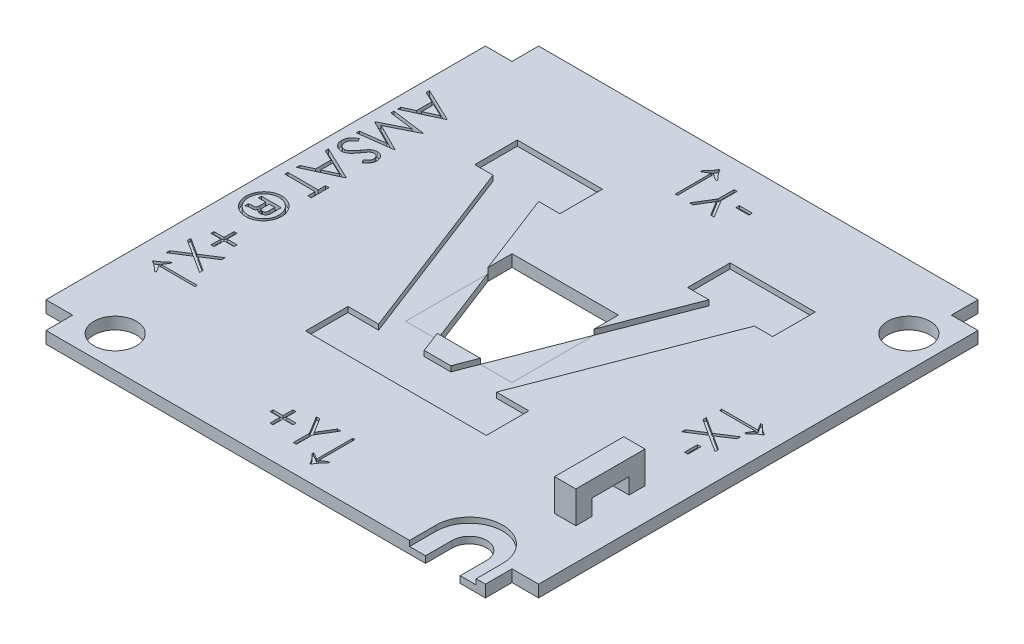
SolidWorks part; units mm, degrees
ref_plane "Front" through (0, 0, 0) normal (0, 0, 1) x (1, 0, 0)
ref_plane "Top" through (0, 0, 0) normal (0, 1, 0) x (1, 0, 0)
ref_plane "Right" through (0, 0, 0) normal (1, 0, 0) x (0, 0, -1)
sketch "Sketch2" plane through (0, 0, 0) normal (0, 1, 0) x (1, 0, 0)
  line L1 (-46.3, 41.3) -> (46.3, 41.3)
  line L2 (-46.3, 41.3) -> (-46.3, -41.3)
  line L3 (-46.3, -41.3) -> (46.3, -41.3)
  line L4 (46.3, 41.3) -> (46.3, -41.3)
  line L5 (-46.3, 41.3) -> (46.3, -41.3) construction
  line L6 (-46.3, -41.3) -> (46.3, 41.3) construction
  line L7 (-41.3, 46.3) -> (41.3, 46.3)
  line L8 (-41.3, 46.3) -> (-41.3, -46.3)
  line L9 (-41.3, -46.3) -> (41.3, -46.3)
  line L10 (41.3, 46.3) -> (41.3, -46.3)
  line L11 (-41.3, 46.3) -> (41.3, -46.3) construction
  line L12 (-41.3, -46.3) -> (41.3, 46.3) construction
  point P0 (0, 0)
  point P6 (0, 0)
  dimension "D1" = 82.6
  dimension "D2" = 92.6
  dimension "D3" = 92.6
  dimension "D4" = 82.6
extrude "Boss-Extrude1" add sketch "Sketch2" along normal blind 2.25 contours L8 L1 L2 L3 | L10 L1 L8 L3 | L10 L3 L8 L9 | L1 L10 L3 L4 | L10 L7 L8 L1 region at (-43.8, 0, 0) region at (0, 0, -43.8) region at (0, 0, 0) region at (43.8, 0, 0) region at (0, 0, 43.8)
sketch "Sketch3" plane through (0, 2.25, 0) normal (0, 1, 0) x (1, 0, 0)
  line L0 (-41.3, 46.3) -> (41.3, 46.3) construction
  line L1 (-46.3, 41.3) -> (-46.3, -41.3) construction
  line L2 (46.3, 41.3) -> (46.3, -41.3) construction
  line L3 (-41.3, -46.3) -> (41.3, -46.3) construction
  circle A0 centre (-34.3, -40.3) radius 4
  circle A1 centre (40.3, 34.3) radius 4
  dimension "D1" = 8
  dimension "D2" = 8
  dimension "D3" = 6
  dimension "D4" = 12
  dimension "D5" = 12
  dimension "D6" = 6
extrude "Cut-Extrude1" cut sketch "Sketch3" against normal blind 10
sketch "Sketch4" plane through (0, 2.25, 0) normal (0, 1, 0) x (1, 0, 0)
  line L1 (-38.2288, 21.7712) -> (-18.2288, 21.7712)
  line L2 (-38.2288, 21.7712) -> (-38.2288, -8.2288)
  line L3 (-38.2288, -8.2288) -> (-18.2288, -8.2288)
  line L4 (-18.2288, 21.7712) -> (-18.2288, -8.2288)
  line L5 (-8.2288, 38.2288) -> (21.7712, 38.2288)
  line L6 (-8.2288, 38.2288) -> (-8.2288, 18.2288)
  line L7 (-8.2288, 18.2288) -> (21.7712, 18.2288)
  line L8 (21.7712, 38.2288) -> (21.7712, 18.2288)
  line L9 (38.2288, -21.7712) -> (18.2288, -21.7712)
  line L10 (38.2288, -21.7712) -> (38.2288, 8.2288)
  line L11 (38.2288, 8.2288) -> (18.2288, 8.2288)
  line L12 (18.2288, -21.7712) -> (18.2288, 8.2288)
  line L13 (8.2288, -18.2288) -> (-21.7712, -18.2288)
  line L14 (8.2288, -18.2288) -> (8.2288, -38.2288)
  line L15 (8.2288, -38.2288) -> (-21.7712, -38.2288)
  line L16 (-21.7712, -18.2288) -> (-21.7712, -38.2288)
  circle A0 centre (0, 0) radius 20 construction
  dimension "D11" = 40
  dimension "D1" = 20
  dimension "D2" = 30
  dimension "D3" = 10
  dimension "D4" = 30
  dimension "D5" = 20
  dimension "D6" = 30
  dimension "D7" = 20
  dimension "D8" = 30
  dimension "D9" = 20
  dimension "D10" = 10
  dimension "D12" = 10
  dimension "D13" = 10
extrude "Cut-Extrude2" [suppressed] cut sketch "Sketch4" against normal blind 10
sketch "Sketch5" plane through (0, 2.25, 0) normal (0, 1, 0) x (1, 0, 0)
  line L0 (30.05, -41.3) -> (30.05, -46.3)
  line L1 (-41.3, -46.3) -> (41.3, -46.3) construction
  line L2 (30.05, -46.3) -> (36.55, -46.3)
  line L3 (36.55, -46.3) -> (36.55, -41.3)
  line L4 (46.3, 41.3) -> (46.3, -41.3) construction
  arc A0 (30.05, -41.3) -> (36.55, -41.3) centre (33.3, -41.3) cw
  dimension "D1" = 5
  dimension "D2" = 3.25
  dimension "D3" = 13
extrude "Cut-Extrude3" cut sketch "Sketch5" against normal blind 10
sketch "Sketch6" plane through (0, 2.25, 0) normal (0, 1, 0) x (1, 0, 0)
  line L0 (27.05, -46.3) -> (27.05, -41.3)
  line L1 (-41.3, -46.3) -> (30.05, -46.3) construction
  line L2 (39.55, -46.3) -> (39.55, -41.3)
  line L4 (27.05, -41.3) -> (30.05, -41.3) construction
  line L5 (36.55, -46.3) -> (41.3, -46.3) construction
  line L8 (36.55, -46.3) -> (36.55, -41.3) construction
  line L9 (39.55, -41.3) -> (36.55, -41.3) construction
  line L10 (27.05, -46.3) -> (30.05, -46.3)
  line L11 (30.05, -46.3) -> (30.05, -41.3)
  line L12 (30.05, -41.3) -> (36.55, -41.3)
  line L13 (36.55, -41.3) -> (36.55, -46.3)
  line L14 (36.55, -46.3) -> (39.55, -46.3)
  arc A0 (27.05, -41.3) -> (39.55, -41.3) centre (33.3, -41.3) cw
  point P13 (39.55, -43.8)
  dimension "D3" = 6.25
  dimension "D1" = 3
  dimension "D2" = 3
extrude "Cut-Extrude4" cut sketch "Sketch6" against normal blind 1
sketch "Sketch7" plane through (0, 2.25, 0) normal (0, 1, 0) x (1, 0, 0)
  line L1 (-10, 10) -> (10, 10)
  line L2 (-10, 10) -> (-10, -10)
  line L3 (-10, -10) -> (10, -10)
  line L4 (10, 10) -> (10, -10)
  line L5 (-10, 10) -> (10, -10) construction
  line L6 (-10, -10) -> (10, 10) construction
  point P0 (0, 0)
  dimension "D1" = 20
  dimension "D2" = 20
extrude "Cut-Extrude5" cut sketch "Sketch7" against normal blind 10
sketch "Sketch9" [suppressed] plane through (0, 2.25, 0) normal (0, 1, 0) x (1, 0, 0)
  line L0 (-38.2288, -8.2288) -> (-18.2288, -8.2288) construction
  line L1 (-38.2288, 21.7712) -> (-31.2481, 21.7712)
  line L2 (-38.2288, 21.7712) -> (-38.2288, -8.2288)
  line L3 (-38.2288, -8.2288) -> (-31.2481, -8.2288)
  line L4 (-31.2481, 21.7712) -> (-31.2481, -8.2288)
extrude "Boss-Extrude2" [suppressed] add sketch "Sketch9" against normal blind 2.25
sketch "Sketch12" plane through (0, 2.25, 0) normal (0, 1, 0) x (1, 0, 0)
  line L1 (-44.3, 29.112) -> (-44.3, -7.0645) construction
  line L2 (-46.3, 41.3) -> (-46.3, -41.3) construction
  text T0 "AMSAT"
  dimension "D1" = 2
extrude "Cut-Extrude9" cut sketch "Sketch12" against normal blind 1
sketch "Sketch18" plane through (0, 2.25, 0) normal (0, 1, 0) x (1, 0, 0)
  line L0 (-24.5745, 21) -> (-11.0745, -14)
  line L1 (-28, 29) -> (-12, 29)
  line L2 (-28, 29) -> (-28, 21)
  line L3 (-28, 21) -> (-12, 21)
  line L4 (-12, 29) -> (-12, 21)
  line L5 (12, 29) -> (28, 29)
  line L6 (12, 29) -> (12, 21)
  line L7 (12, 21) -> (28, 21)
  line L8 (28, 29) -> (28, 21)
  line L9 (-16.8241, -14) -> (17.1759, -14)
  line L10 (-16.8241, -14) -> (-16.8241, -22)
  line L11 (-16.8241, -22) -> (17.1759, -22)
  line L12 (17.1759, -14) -> (17.1759, -22)
  line L13 (-11.0745, -14) -> (-2.5, -14)
  line L14 (-2.5, -14) -> (-16, 21)
  line L15 (2.5, -14) -> (16, 21)
  line L16 (24.5745, 21) -> (11.0745, -14)
  line L17 (0, 0) -> (0, -14) construction
  line L18 (-24.5745, 21) -> (-16, 21) construction
  line L19 (-10, -10) -> (10, -10) construction
  line L20 (16, 21) -> (24.5745, 21) construction
  point P25 (20, 21)
  dimension "D1" = 8
  dimension "D2" = 8
  dimension "D3" = 2.5
  dimension "D4" = 2.5
  dimension "D5" = 34
  dimension "D6" = 8
  dimension "D7" = 8
  dimension "D8" = 8
  dimension "D9" = 16
  dimension "D10" = 16
  dimension "D11" = 35
  dimension "D12" = 4
  dimension "D13" = 12
  dimension "D14" = 12
  dimension "D15" = 4
  dimension "D16" = 4
sketch "Sketch21" plane through (0, 2.25, 0) normal (0, 1, 0) x (1, 0, 0)
  line L0 (-44.3, 28.7864) -> (-44.3, -17.5036) construction
  line L1 (-44.3, -2.3211) -> (-37.9588, -2.3211) construction
  line L2 (-44.3, -2.3211) -> (-44.3, -24.4995) construction
  line L3 (-39.1712, -4.1935) -> (-39.1712, -5.7759)
  line L4 (-41.8971, -7.1243) -> (-42.3194, -7.1243)
  line L5 (-42.8168, -7.2909) -> (-42.916, -7.3685)
  line L6 (-42.916, -7.3685) -> (-42.916, -6.6358)
  line L7 (-42.4276, -6.5747) -> (-42.0205, -6.5544)
  line L8 (-41.5321, -5.7696) -> (-41.5321, -4.7634)
  line L9 (-41.5321, -4.7634) -> (-42.916, -4.7634)
  line L10 (-42.916, -4.7634) -> (-42.916, -4.1935)
  line L11 (-42.916, -4.1935) -> (-39.1712, -4.1935)
  line L12 (-39.8224, -4.7634) -> (-40.8808, -4.7634)
  line L13 (-40.8808, -4.7634) -> (-40.8808, -5.7288)
  line L14 (-39.8224, -5.767) -> (-39.8224, -4.7634)
  spline S0 degree 3 poles (-41.0372, -8.9967) (-41.185, -8.9949) (-41.4059, -8.984) (-41.695, -8.9354) (-41.9066, -8.8858) (-42.1141, -8.8224) (-42.3174, -8.7439) (-42.517, -8.6528) (-42.7113, -8.5469) (-42.8987, -8.4297) (-43.0761, -8.3001) (-43.2448, -8.1618) (-43.4023, -8.0112) (-43.5504, -7.8507) (-43.6877, -7.6793) (-43.8172, -7.499) (-43.9327, -7.3071) (-44.0386, -7.1097) (-44.1298, -6.9072) (-44.2087, -6.7017) (-44.27, -6.4915) (-44.3201, -6.2789) (-44.3686, -5.9894) (-44.3797, -5.7685) (-44.3814, -5.6207) knots 0 0 0 0 0.084082 0.125371 0.166472 0.207567 0.248614 0.290246 0.3322 0.374331 0.415745 0.457006 0.498264 0.539545 0.581027 0.623028 0.665647 0.708239 0.750309 0.791807 0.833294 0.874629 0.915918 1 1 1 1
  spline S1 degree 3 poles (-44.3814, -5.6207) (-44.3796, -5.473) (-44.3688, -5.2515) (-44.3197, -4.9619) (-44.2724, -4.7485) (-44.2073, -4.5397) (-44.132, -4.3329) (-44.0394, -4.1309) (-43.9357, -3.9326) (-43.8194, -3.7417) (-43.6918, -3.56) (-43.5527, -3.39) (-43.405, -3.2288) (-43.2468, -3.0786) (-43.0789, -2.9382) (-42.9, -2.8096) (-42.7123, -2.6922) (-42.5189, -2.5849) (-42.3193, -2.4938) (-42.1173, -2.4139) (-41.9108, -2.3508) (-41.7014, -2.3009) (-41.4165, -2.2526) (-41.199, -2.2413) (-41.0538, -2.2397) knots 0 0 0 0 0.084269 0.125889 0.167262 0.208679 0.250411 0.292575 0.335148 0.377862 0.419817 0.461544 0.502916 0.544266 0.585774 0.627475 0.6697 0.711864 0.753369 0.794595 0.83555 0.876272 0.917177 1 1 1 1
  spline S2 degree 3 poles (-41.0538, -2.2397) (-40.9072, -2.2412) (-40.6876, -2.2528) (-40.4002, -2.3007) (-40.1891, -2.3508) (-39.981, -2.4142) (-39.777, -2.4935) (-39.5756, -2.5852) (-39.38, -2.6921) (-39.1899, -2.8092) (-39.0095, -2.9382) (-38.8408, -3.0786) (-38.6806, -3.2276) (-38.5319, -3.388) (-38.3938, -3.5593) (-38.2673, -3.7414) (-38.1498, -3.9315) (-38.0469, -4.1294) (-37.9537, -4.3306) (-37.8781, -4.5369) (-37.8155, -4.7468) (-37.7653, -4.9599) (-37.7203, -5.2511) (-37.704, -5.4722) (-37.7058, -5.6207) knots 0 0 0 0 0.083231 0.124457 0.16526 0.206291 0.24781 0.289377 0.331805 0.374278 0.416018 0.457555 0.498758 0.540138 0.581556 0.62355 0.665898 0.708311 0.750097 0.791671 0.832863 0.874368 0.915793 1 1 1 1
  spline S3 degree 3 poles (-37.7058, -5.6207) (-37.7041, -5.7692) (-37.7201, -5.9904) (-37.7656, -6.281) (-37.8141, -6.4939) (-37.8766, -6.703) (-37.9531, -6.9082) (-38.0436, -7.1096) (-38.1476, -7.3057) (-38.2632, -7.4954) (-38.39, -7.6758) (-38.5281, -7.8455) (-38.6763, -8.0054) (-38.8353, -8.1553) (-39.0044, -8.2956) (-39.1852, -8.4244) (-39.3744, -8.5433) (-39.571, -8.6495) (-39.7707, -8.743) (-39.974, -8.8209) (-40.1807, -8.8842) (-40.3903, -8.9357) (-40.6754, -8.9835) (-40.8923, -8.9953) (-41.0372, -8.9967) knots 0 0 0 0 0.084514 0.12609 0.167457 0.208799 0.250299 0.292137 0.334491 0.376661 0.41861 0.459992 0.501181 0.542701 0.584388 0.62628 0.669037 0.711619 0.753439 0.794572 0.835522 0.876529 0.917429 1 1 1 1
  spline S4 degree 3 poles (-41.0436, -8.5082) (-40.9191, -8.5073) (-40.7328, -8.4969) (-40.4891, -8.4555) (-40.3097, -8.4134) (-40.1331, -8.359) (-39.9597, -8.2909) (-39.789, -8.2118) (-39.6215, -8.1223) (-39.4605, -8.0203) (-39.307, -7.9101) (-39.1618, -7.7914) (-39.0277, -7.662) (-38.8994, -7.5267) (-38.7831, -7.3804) (-38.6722, -7.2281) (-38.5746, -7.0654) (-38.4851, -6.898) (-38.4079, -6.7262) (-38.3408, -6.5515) (-38.2878, -6.3727) (-38.2454, -6.191) (-38.2067, -5.9431) (-38.1945, -5.7546) (-38.1942, -5.6284) knots 0 0 0 0 0.083087 0.124099 0.164782 0.205936 0.24722 0.288982 0.331375 0.373829 0.415981 0.457375 0.498787 0.540211 0.581645 0.623403 0.665799 0.70806 0.74996 0.791407 0.832749 0.874259 0.915784 1 1 1 1
  spline S5 degree 3 poles (-38.1942, -5.6284) (-38.1944, -5.5012) (-38.2068, -5.3115) (-38.2452, -5.0623) (-38.288, -4.8798) (-38.341, -4.6998) (-38.4078, -4.5229) (-38.4851, -4.3486) (-38.5745, -4.1786) (-38.6722, -4.0134) (-38.7831, -3.8586) (-38.8991, -3.7098) (-39.0273, -3.573) (-39.1623, -3.4439) (-39.3061, -3.3234) (-39.461, -3.2151) (-39.6214, -3.1127) (-39.7891, -3.0235) (-39.9597, -2.9435) (-40.1344, -2.878) (-40.3116, -2.8224) (-40.4925, -2.7811) (-40.7387, -2.7392) (-40.9267, -2.7291) (-41.0525, -2.7281) knots 0 0 0 0 0.084266 0.125816 0.167074 0.208434 0.250155 0.292315 0.334816 0.377436 0.419398 0.46102 0.502398 0.543559 0.58488 0.626613 0.668809 0.710945 0.752453 0.793648 0.834552 0.875536 0.916576 1 1 1 1
  spline S6 degree 3 poles (-41.0525, -2.7281) (-41.1774, -2.7291) (-41.3641, -2.7393) (-41.6082, -2.7809) (-41.7874, -2.8226) (-41.963, -2.878) (-42.1364, -2.9435) (-42.3058, -3.0235) (-42.4721, -3.1128) (-42.6312, -3.2146) (-42.7838, -3.3243) (-42.9273, -3.4435) (-43.0617, -3.573) (-43.1872, -3.7114) (-43.305, -3.8587) (-43.4144, -4.0147) (-43.5132, -4.18) (-43.6014, -4.3506) (-43.6797, -4.5245) (-43.7461, -4.7011) (-43.7994, -4.8814) (-43.8416, -5.064) (-43.8807, -5.3127) (-43.8926, -5.5017) (-43.8929, -5.6284) knots 0 0 0 0 0.083161 0.124071 0.164652 0.205433 0.246513 0.287914 0.329953 0.372063 0.413487 0.454957 0.496062 0.537606 0.579157 0.621501 0.664274 0.707178 0.749231 0.791103 0.832611 0.874292 0.915713 1 1 1 1
  spline S7 degree 3 poles (-43.8929, -5.6284) (-43.8929, -5.7543) (-43.8801, -5.9421) (-43.8424, -6.1896) (-43.7975, -6.3704) (-43.745, -6.5493) (-43.6783, -6.7246) (-43.6005, -6.8972) (-43.5107, -7.0654) (-43.4099, -7.2275) (-43.3028, -7.3836) (-43.1836, -7.5283) (-43.0571, -7.6647) (-42.9241, -7.794) (-42.7803, -7.9121) (-42.6295, -8.0235) (-42.4693, -8.1228) (-42.3041, -8.2137) (-42.1344, -8.2921) (-41.9611, -8.3589) (-41.7848, -8.4137) (-41.604, -8.4556) (-41.3577, -8.4967) (-41.1694, -8.5076) (-41.0436, -8.5082) knots 0 0 0 0 0.083922 0.125442 0.166735 0.208071 0.249777 0.291673 0.33431 0.376848 0.418899 0.460506 0.501732 0.542934 0.584104 0.625793 0.667851 0.709742 0.751498 0.792411 0.833559 0.874512 0.916077 1 1 1 1
  spline S8 degree 3 poles (-39.1712, -5.7759) (-39.1708, -5.862) (-39.1733, -5.9864) (-39.1852, -6.1455) (-39.1983, -6.2502) (-39.2129, -6.3455) (-39.2316, -6.431) (-39.2548, -6.5064) (-39.2878, -6.5944) (-39.3428, -6.6921) (-39.4239, -6.7982) (-39.5231, -6.8928) (-39.6383, -6.9754) (-39.7682, -7.0407) (-39.9595, -7.1088) (-40.115, -7.1221) (-40.2193, -7.1243) knots 0 0 0 0 0.131786 0.190365 0.24397 0.293257 0.337811 0.377839 0.413992 0.48137 0.548473 0.617773 0.690341 0.764636 0.839543 1 1 1 1
  spline S9 degree 3 poles (-40.2193, -7.1243) (-40.3084, -7.1267) (-40.4743, -7.1117) (-40.6384, -7.082) (-40.7116, -7.0556) knots 0 0 0 0 0.534352 1 1 1 1
  spline S10 degree 3 poles (-40.7116, -7.0556) (-40.7738, -7.0206) (-40.8956, -6.9017) (-40.9959, -6.7655) (-41.0474, -6.6816) knots 0 0 0 0 0.418044 1 1 1 1
  spline S11 degree 3 poles (-41.0474, -6.6816) (-41.0832, -6.7597) (-41.1465, -6.8646) (-41.2512, -6.9786) (-41.3362, -7.0387) (-41.4395, -7.0787) (-41.6269, -7.1176) (-41.7836, -7.1254) (-41.8971, -7.1243) knots 0 0 0 0 0.248758 0.352185 0.446606 0.54746 0.670874 1 1 1 1
  spline S12 degree 3 poles (-42.3194, -7.1243) (-42.412, -7.123) (-42.5915, -7.1489) (-42.751, -7.2354) (-42.8168, -7.2909) knots 0 0 0 0 0.518993 1 1 1 1
  spline S13 degree 3 poles (-42.916, -6.6358) (-42.8417, -6.6196) (-42.6791, -6.5953) (-42.5156, -6.5795) (-42.4276, -6.5747) knots 0 0 0 0 0.463214 1 1 1 1
  spline S14 degree 3 poles (-42.0205, -6.5544) (-41.9567, -6.5474) (-41.8665, -6.5384) (-41.762, -6.5022) (-41.7047, -6.4705) (-41.6609, -6.4305) (-41.6229, -6.3858) (-41.5938, -6.3323) (-41.5693, -6.2685) (-41.5517, -6.1846) (-41.5345, -6.0164) (-41.5323, -5.8743) (-41.5321, -5.7696) knots 0 0 0 0 0.179641 0.249904 0.307061 0.360638 0.414345 0.469893 0.529361 0.604464 0.707939 1 1 1 1
  spline S15 degree 3 poles (-40.8808, -5.7288) (-40.8825, -5.852) (-40.872, -6.054) (-40.8293, -6.2537) (-40.7905, -6.3242) knots 0 0 0 0 0.607223 1 1 1 1
  spline S16 degree 3 poles (-40.7905, -6.3242) (-40.7508, -6.398) (-40.6185, -6.5247) (-40.4384, -6.5558) (-40.3478, -6.5544) knots 0 0 0 0 0.477173 1 1 1 1
  spline S17 degree 3 poles (-40.3478, -6.5544) (-40.2679, -6.5558) (-40.1514, -6.538) (-40.0196, -6.4657) (-39.9569, -6.4036) (-39.9185, -6.3418) (-39.8911, -6.2869) (-39.8708, -6.2218) (-39.8525, -6.1484) (-39.8392, -6.0658) (-39.8246, -5.9379) (-39.8243, -5.8369) (-39.8224, -5.767) knots 0 0 0 0 0.220304 0.315334 0.409336 0.459153 0.514956 0.577646 0.646091 0.722966 0.807444 1 1 1 1
extrude "Cut-Extrude10" cut sketch "Sketch21" against normal blind 1 contours S14 L7 S13 L6 L5 S12 L4 S11 S10 S9 S8 L3 L11 L10 L9 L8 S17 S16 S15 L13 L12 L14 | S3 S2 S1 S0 S7 S6 S5 S4 region at (-39.2203, 2.25, 4.9847) region at (-43.3391, 2.25, 7.9367)
extrude "Cut-Extrude7" cut sketch "Sketch18" against normal blind 1 contours L9 L14 L3 L0 | L16 L7 L15 L9 | L4 L1 L2 L3 | L8 L5 L6 L7 | L12 L9 L10 L11 region at (-13.5372, 2.25, -3.5) region at (-20, 2.25, -25) region at (0.1759, 2.25, 18) region at (13.5372, 2.25, -3.5) region at (20, 2.25, -25)
sketch "Sketch19" plane through (0, 2.25, 0) normal (0, 1, 0) x (1, 0, 0)
  line L0 (-10, 5.4444) -> (-4.0429, -10)
  line L1 (-4.0429, -10) -> (4.0429, -10) construction
  line L2 (-2.5, -14) -> (-4.0429, -10) construction
  line L4 (4.0429, -10) -> (10, 5.4444)
  line L5 (10, 5.4444) -> (10, -10)
  line L6 (10, 5.4444) -> (10, -10) construction
  line L7 (10, -10) -> (4.0429, -10) construction
  line L8 (10, -10) -> (-10, -10)
  line L9 (-10, -10) -> (-10, 5.4444)
extrude "Boss-Extrude3" add sketch "Sketch19" against normal blind 2.25 separate body contours L9 L8 L0 | L8 L5 L4 region at (8.0143, 2.25, 4.8519) region at (-8.0143, 2.25, 4.8519)
sketch "Sketch20" plane through (0, 2.25, 0) normal (0, 1, 0) x (1, 0, 0)
  line L0 (-10, 5.4444) -> (-10, -10)
  line L1 (-10, -10) -> (-4.0429, -10)
  line L2 (-4.0429, -10) -> (-10, 5.4444)
  line L3 (4.0429, -10) -> (10, 5.4444)
  line L4 (10, 5.4444) -> (10, -10)
  line L5 (10, -10) -> (4.0429, -10)
extrude "Cut-Extrude8" cut sketch "Sketch20" against normal blind 1
sketch "Sketch22" plane through (0, 2.25, 0) normal (0, 1, 0) x (1, 0, 0)
  line L0 (-46.3, -41.3) -> (46.3, -41.3) construction
  line L1 (-46.3, 41.3) -> (-46.3, -41.3) construction
  line L2 (46.3, 41.3) -> (46.3, -41.3) construction
  line L3 (-36.3, -46.3) -> (-36.3, 46.3) construction
  line L4 (-41.3, -46.3) -> (27.05, -46.3) construction
  line L5 (-41.3, 46.3) -> (41.3, 46.3) construction
  line L6 (-46.3, 41.3) -> (46.3, 41.3) construction
  line L7 (41.3, 46.3) -> (41.3, -46.3) construction
  text T0 "↑X+                "
  text T1 "+Y↓"
  text T2 "↓Y-"
  text T3 "↓X-"
  dimension "D1" = 10
  dimension "D2" = 5
  dimension "D3" = 5
  dimension "D4" = 5
extrude "Cut-Extrude11" cut sketch "Sketch22" against normal blind 0.5
sketch "Sketch23" plane through (0, 2.25, 0) normal (0, 1, 0) x (1, 0, 0)
  line L0 (-41.3, -46.3) -> (27.05, -46.3) construction
  line L1 (36.3, -15.3) -> (40.3, -15.3)
  line L2 (36.3, -15.3) -> (36.3, -18.3)
  line L3 (36.3, -18.3) -> (40.3, -18.3)
  line L4 (40.3, -15.3) -> (40.3, -18.3)
  line L5 (36.3, -25.3) -> (40.3, -25.3)
  line L6 (36.3, -25.3) -> (36.3, -28.3)
  line L7 (36.3, -28.3) -> (40.3, -28.3)
  line L8 (40.3, -25.3) -> (40.3, -28.3)
  line L9 (46.3, 41.3) -> (46.3, -41.3) construction
  line L10 (36.3, -18.3) -> (36.3, -25.3) construction
  point P10 (40.3, -16.8)
  dimension "D1" = 7
  dimension "D2" = 3
  dimension "D3" = 3
  dimension "D4" = 4
  dimension "D5" = 4
  dimension "D6" = 18
  dimension "D7" = 6
extrude "Boss-Extrude4" add sketch "Sketch23" along normal blind 3
sketch "Sketch24" plane through (0, 5.25, 0) normal (0, 1, 0) x (1, 0, 0)
  line L1 (36.3, -15.3) -> (40.3, -15.3)
  line L2 (36.3, -15.3) -> (36.3, -28.3)
  line L3 (36.3, -28.3) -> (40.3, -28.3)
  line L4 (40.3, -15.3) -> (40.3, -28.3)
extrude "Boss-Extrude5" add sketch "Sketch24" along normal blind 3
